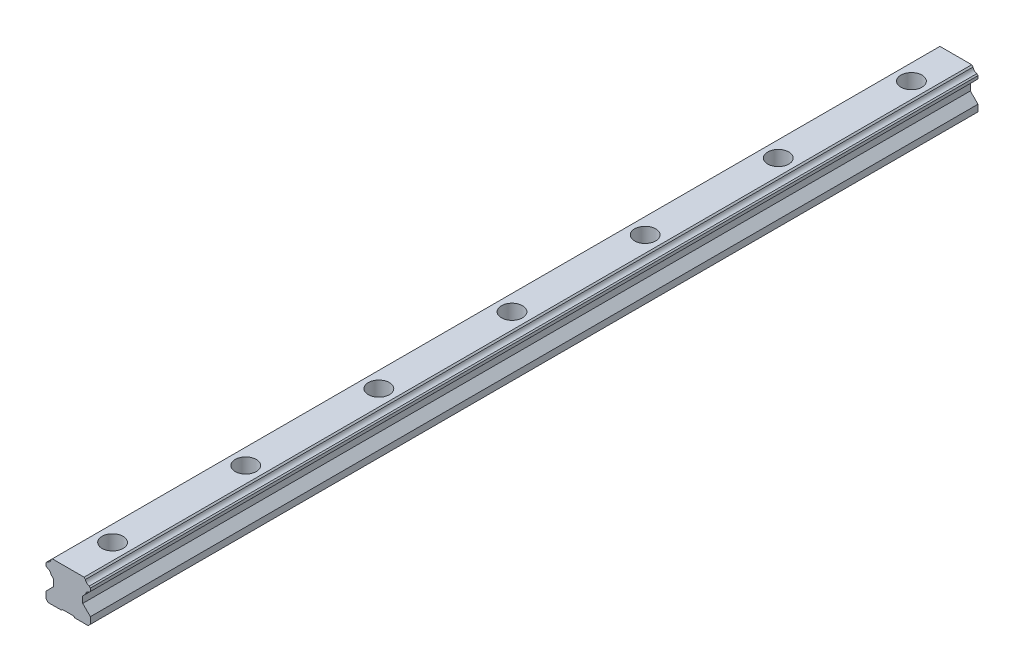
SolidWorks part; units mm, degrees
material "Plain Carbon Steel"
ref_plane "Front Plane" through (0, 0, 0) normal (0, 0, 1) x (1, 0, 0)
ref_plane "Top Plane" through (0, 0, 0) normal (0, 1, 0) x (1, 0, 0)
ref_plane "Right Plane" through (0, 0, 0) normal (1, 0, 0) x (0, 0, -1)
sketch "Sketch1" plane through (0, 0, 0) normal (0, 0, 1) x (1, 0, 0)
  line L0 (-10, -10.4945) -> (-10, -13.4946)
  line L1 (-10, -13.4946) -> (-9, -14.4946)
  line L2 (-9, -14.4946) -> (-3, -14.4946)
  line L3 (-3, -14.4946) -> (-2.5, -13.9946)
  line L4 (-2.5, -13.9946) -> (2.5, -13.9946)
  line L5 (6.55, -7.0447) -> (10, -10.4945)
  line L6 (6.55, -4.1154) -> (6.55, -7.0447)
  line L7 (7.7679, -2.8995) -> (6.55, -4.1154)
  line L8 (10, -0.6654) -> (9.4727, -1.1802)
  line L9 (10, 0.6654) -> (10, -0.6654)
  line L10 (9.4727, 1.1928) -> (10, 0.6654)
  line L11 (7.16, 3.5054) -> (7.7679, 2.8975)
  line L12 (3, -14.4946) -> (2.5, -13.9946)
  line L13 (9, -14.4946) -> (3, -14.4946)
  line L14 (10, -13.4946) -> (9, -14.4946)
  line L15 (10, -10.4945) -> (10, -13.4946)
  line L16 (7.16, 3.5054) -> (-7.16, 3.5054)
  line L17 (-7.16, 3.5054) -> (-7.7679, 2.8975)
  line L18 (-9.4727, 1.1928) -> (-10, 0.6654)
  line L19 (-10, 0.6654) -> (-10, -0.6654)
  line L20 (-10, -0.6654) -> (-9.4727, -1.1802)
  line L21 (-7.7679, -2.8995) -> (-6.55, -4.1154)
  line L22 (-6.55, -4.1154) -> (-6.55, -7.0447)
  line L23 (-6.55, -7.0447) -> (-10, -10.4945)
  line L24 (0, -14.4946) -> (0, -13.9946) construction
  line L25 (0, -13.9946) -> (0, 3.5054) construction
  line L26 (11, 0) -> (-11, 0) construction
  arc A0 (9.4727, -1.1802) -> (7.7679, -2.8995) centre (9.8039, -3.2134) ccw
  arc A1 (7.7679, 2.8975) -> (9.4727, 1.1928) centre (9.8015, 3.2263) ccw
  arc A2 (-7.7679, 2.8975) -> (-9.4727, 1.1928) centre (-9.8015, 3.2263) cw
  arc A3 (-9.4727, -1.1802) -> (-7.7679, -2.8995) centre (-9.8039, -3.2134) cw
  point P38 (10, 0)
  dimension "D17" = 2.06
  dimension "D1" = 20
  dimension "D2" = 1
  dimension "D3" = 1
  dimension "D4" = 0.5
  dimension "D5" = 0.5
  dimension "D6" = 6
  dimension "D7" = 18
  dimension "D8" = 4.0001
  dimension "D9" = 10.55
  dimension "D10" = 13.1001
  dimension "D11" = 15.5359
  dimension "D12" = 0.6079
  dimension "D13" = 0.6079
  dimension "D14" = 17.5
  dimension "D15" = 0.5273
  dimension "D16" = 0.5273
  dimension "D18" = 1.2159
  dimension "D19" = 0.5148
  dimension "D20" = 6.4049
  dimension "D21" = 2.84
  dimension "D22" = 4.1708
extrude "Boss-Extrude1" add sketch "Sketch1" against normal mid plane 400
sketch "Sketch2" plane through (0, 0, 0) normal (1, 0, 0) x (0, 0, -1)
  line L0 (-180, 3.5054) -> (-180, -14.4946)
  line L1 (200, 3.5054) -> (-200, 3.5054) construction
  line L2 (200, -14.4946) -> (-200, -14.4946) construction
  line L3 (-180, -14.4946) -> (-183, -14.4946)
  line L4 (-183, -14.4946) -> (-183, -4.9946)
  line L5 (-183, -4.9946) -> (-184.75, -4.9946)
  line L6 (-184.75, -4.9946) -> (-184.75, 3.5054)
  line L7 (-184.75, 3.5054) -> (-180, 3.5054)
  line L8 (-200, -7.0447) -> (-200, -4.1154) construction
  point P12 (-200, -5.58)
  dimension "D1" = 3
  dimension "D2" = 4.75
  dimension "D3" = 8.5
  dimension "D4" = 20
revolve "Cut-Revolve1" cut sketch "Sketch2" angle 360 about L0
pattern_linear "LPattern1" count 7 spacing 60 along (0, 0, -1) of "Cut-Revolve1"
equation "\"Length\"= 400"
equation "\"Pitch\"= 60mm"
equation "\"Holes\"= int ( ( \"Length\" + \"Pitch\" / 2 ) / \"Pitch\" )"
equation "\"EndSpacing\"= ( \"Length\" - \"Pitch\" * ( \"Holes\" - 1 ) ) / 2"
equation "\"D4@Sketch2\"=\"EndSpacing\""
equation "\"D3@LPattern1\"=\"Pitch\""
equation "\"D1@LPattern1\"=\"Holes\""
equation "\"D1@Boss-Extrude1\"=\"Length\""
